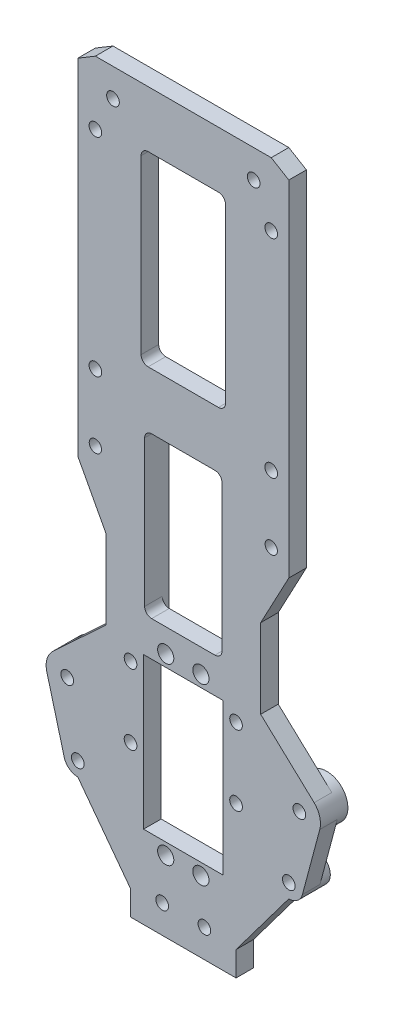
SolidWorks part; units mm, degrees
ref_plane "正面" through (0, 0, 0) normal (0, 0, 1) x (1, 0, 0)
ref_plane "平面" through (0, 0, 0) normal (0, 1, 0) x (1, 0, 0)
ref_plane "右側面" through (0, 0, 0) normal (1, 0, 0) x (0, 0, -1)
sketch "ｽｹｯﾁ1" plane through (0, 0, 0) normal (0, 0, 1) x (1, 0, 0)
  line L4 (7.743, 43.8914) -> (57.743, 43.8914)
  line L10 (17.743, -156.1086) -> (17.743, -163.1086)
  line L14 (65.743, -113.1086) -> (32.743, -113.1086) construction
  line L16 (32.743, 95.8492) -> (32.743, -203.2608) construction
  line L17 (32.743, -113.1086) -> (-0.257, -113.1086) construction
  line L21 (17.743, -163.1086) -> (47.743, -163.1086)
  line L22 (47.743, -163.1086) -> (47.743, -156.1086)
  line L25 (65.743, -89.0701) -> (65.743, -113.1086) construction
  line L26 (26.743, -155.1086) -> (38.743, -155.1086) construction
  line L27 (-0.257, -123.1086) -> (-0.257, -103.1086) construction
  line L34 (2.743, -132.1086) -> (62.743, -132.1086) construction
  line L36 (-41.4825, 1.8914) -> (140.922, 1.8914) construction
  line L38 (10.743, -94.6763) -> (10.743, -72.1086)
  line L39 (54.743, -94.6763) -> (54.743, -72.1086)
  line L41 (54.743, -72.1086) -> (62.743, -57.1086)
  line L42 (62.743, -57.1086) -> (62.743, 40.8914)
  line L43 (16.0734, -118.1086) -> (50.1368, -118.1086) construction
  line L48 (27.743, -93.3086) -> (37.743, -93.3086) construction
  line L49 (21.443, -96.6086) -> (44.043, -96.6086)
  line L50 (21.443, -96.6086) -> (21.443, -139.6086)
  line L52 (44.043, -96.6086) -> (44.043, -139.6086)
  line L53 (21.443, -96.6086) -> (44.043, -139.6086) construction
  line L54 (21.443, -139.6086) -> (44.043, -96.6086) construction
  line L55 (37.743, -93.3086) -> (37.743, -142.9086) construction
  line L56 (37.743, -142.9086) -> (27.743, -142.9086) construction
  line L57 (27.743, -142.9086) -> (27.743, -93.3086) construction
  line L58 (62.743, 40.8914) -> (57.743, 43.8914)
  line L59 (7.743, 43.8914) -> (2.743, 40.8914)
  line L60 (2.743, 40.8914) -> (2.743, -57.1086)
  line L61 (2.743, -57.1086) -> (10.743, -72.1086)
  line L62 (69.9508, -108.8314) -> (54.743, -94.6763)
  line L64 (-4.5045, -108.8708) -> (10.743, -94.6763)
  line L65 (62.743, -136.1086) -> (47.743, -156.1086)
  line L66 (21.443, -139.6086) -> (32.743, -139.6086)
  line L67 (20.743, 27.8914) -> (44.743, 27.8914)
  line L68 (20.743, 27.8914) -> (20.743, -25.1086)
  line L69 (20.743, -25.1086) -> (44.743, -25.1086)
  line L70 (44.743, 27.8914) -> (44.743, -25.1086)
  line L71 (44.043, -139.6086) -> (32.743, -139.6086)
  line L73 (21.743, -86.6086) -> (43.743, -86.6086)
  line L82 (21.743, -86.6086) -> (21.743, -41.1086)
  line L83 (21.743, -41.1086) -> (43.743, -41.1086)
  line L84 (43.743, -86.6086) -> (43.743, -41.1086)
  line L93 (17.743, -156.1086) -> (2.743, -136.1086)
  line L95 (71.5402, -114.6555) -> (66.6078, -133.1399)
  line L96 (-6.0542, -114.6555) -> (-1.1218, -133.1399)
  line L97 (62.743, -136.1086) -> (2.743, -136.1086) construction
  line L98 (-1.1218, -133.1399) -> (80.8725, -133.1399) construction
  line L99 (12.743, 35.8914) -> (57.743, 35.8914) construction
  line L100 (4.743, -33.1086) -> (60.743, -33.1086) construction
  line L101 (-6.0542, -114.6555) -> (71.5402, -114.6555) construction
  line L102 (62.743, -57.1086) -> (2.743, -57.1086) construction
  line L103 (10.743, -72.1086) -> (54.743, -72.1086) construction
  circle A14 centre (27.743, -93.3086) radius 2.3
  circle A15 centre (37.743, -93.3086) radius 2.3
  circle A16 centre (27.743, -142.9086) radius 2.3
  circle A17 centre (37.743, -142.9086) radius 2.3
  circle A18 centre (-0.257, -113.1086) radius 1.8
  circle A20 centre (62.743, -132.1086) radius 1.8
  circle A21 centre (2.743, -132.1086) radius 1.8
  circle A30 centre (65.743, -113.1086) radius 1.8
  circle A35 centre (26.743, -155.1086) radius 1.8
  circle A36 centre (38.743, -155.1086) radius 1.8
  arc A38 (-6.0542, -114.6555) -> (-4.5045, -108.8708) centre (-0.257, -113.1086) cw
  arc A39 (71.5402, -114.6555) -> (69.9508, -108.8314) centre (65.743, -113.1086) ccw
  arc A40 (-1.1218, -133.1399) -> (2.743, -136.1086) centre (2.743, -132.1086) ccw
  arc A41 (66.6078, -133.1399) -> (62.743, -136.1086) centre (62.743, -132.1086) cw
  circle A42 centre (52.743, 35.8914) radius 1.8
  circle A43 centre (12.743, 35.8914) radius 1.8
  circle A44 centre (57.743, -33.1086) radius 1.8
  circle A45 centre (7.743, -33.1086) radius 1.8
  point P30 (32.743, -118.1086)
  point P49 (32.743, -142.9086)
  point P62 (32.743, 6.8914)
  dimension "D5" = 115
  dimension "D12" = 3
  dimension "D16" = 25
  dimension "D19" = 3.6
  dimension "D27" = 3.6
  dimension "D28" = 20
  dimension "D34" = 24.8
  dimension "D9" = 30
  dimension "D37" = 4.6
  dimension "D38" = 25
  dimension "D48" = 3.6
  dimension "D6" = 6
  dimension "D7" = 6
  dimension "D21" = 3.6
  dimension "D26" = 20
  dimension "D2" = 33
  dimension "D3" = 19
  dimension "D4" = 15
  dimension "D8" = 43
  dimension "D10" = 42
  dimension "D11" = 30
  dimension "D13" = 25
  dimension "D14" = 33
  dimension "D15" = 30
  dimension "D17" = 22.6
  dimension "D18" = 43
  dimension "D20" = 30
  dimension "D22" = 34
  dimension "D23" = 35
  dimension "D24" = 50
  dimension "D25" = 15
  dimension "D29" = 8
  dimension "D30" = 6
  dimension "D31" = 6
  dimension "D32" = 5
  dimension "D33" = 24.8
  dimension "D35" = 5
  dimension "D36" = 5
  dimension "D39" = 24
  dimension "D40" = 8
  dimension "D41" = 10
  dimension "D42" = 25
  dimension "D43" = 8
  dimension "D44" = 8
  dimension "D45" = 12
  dimension "D46" = 22
  dimension "D47" = 22
  dimension "D49" = 59
  dimension "D50" = 4
  dimension "D51" = 15
extrude "ﾎﾞｽ - 押し出し1" add sketch "ｽｹｯﾁ1" along normal blind 5
sketch "ｽｹｯﾁ3" plane through (0, 0, 5) normal (0, 0, 1) x (1, 0, 0)
  line L0 (-20.5754, -52.1086) -> (71.6894, -52.1086) construction
  line L5 (-41.4825, 1.8914) -> (140.922, 1.8914) construction
  line L7 (57.743, -20.728) -> (57.743, -85.4424) construction
  line L9 (-13.1542, 25.8914) -> (75.6263, 25.8914) construction
  line L10 (32.743, 95.8492) -> (32.743, -203.2608) construction
  line L11 (7.743, -20.728) -> (7.743, -90.4395) construction
  circle A0 centre (7.743, -52.1086) radius 1.75
  circle A1 centre (57.743, -52.1086) radius 1.75
  circle A4 centre (7.743, 25.8914) radius 1.8
  circle A5 centre (57.743, 25.8914) radius 1.8
  dimension "D7" = 3.6
  dimension "D1" = 54
  dimension "D2" = 78
  dimension "D3" = 25
  dimension "D4" = 25
  dimension "D5" = 25
  dimension "D6" = 25
extrude "ｶｯﾄ - 押し出し1" cut sketch "ｽｹｯﾁ3" against normal through all
sketch "ｽｹｯﾁ4" plane through (0, 0, 0) normal (0, 0, -1) x (-1, 0, 0)
  circle A0 centre (-7.743, 25.8914) radius 3
  circle A2 centre (-57.743, 25.8914) radius 3
  circle A6 centre (-7.743, -52.1086) radius 3
  circle A7 centre (-57.743, -52.1086) radius 3
  dimension "D1" = 6
sketch "ｽｹｯﾁ5" plane through (0, 0, 5) normal (0, 0, 1) x (1, 0, 0)
  line L0 (12.2125, -100.1086) -> (53.2964, -100.1086) construction
  line L1 (11.1967, -120.1086) -> (53.2964, -120.1086) construction
  line L2 (32.743, 95.8492) -> (32.743, -203.2608) construction
  line L4 (16.0734, -118.1086) -> (50.1368, -118.1086) construction
  circle A2 centre (47.743, -100.1086) radius 1.8
  circle A3 centre (47.743, -120.1086) radius 1.8
  circle A4 centre (17.743, -120.1086) radius 1.8
  circle A5 centre (17.743, -100.1086) radius 1.8
  dimension "D2" = 3.6
  dimension "D1" = 20
  dimension "D3" = 15
  dimension "D4" = 15
  dimension "D5" = 2
extrude "ｶｯﾄ - 押し出し3" cut sketch "ｽｹｯﾁ5" against normal blind 6
sketch "ｽｹｯﾁ7" plane through (0, 0, 0) normal (0, 0, -1) x (-1, 0, 0)
  circle A0 centre (-65.743, -113.1086) radius 6
  circle A1 centre (-62.743, -132.1086) radius 4
  circle A2 centre (0.257, -113.1086) radius 6
  circle A3 centre (-2.743, -132.1086) radius 4
  circle A4 centre (0.257, -113.1086) radius 1.8
  circle A5 centre (-2.743, -132.1086) radius 1.8
  circle A6 centre (-65.743, -113.1086) radius 1.8
  circle A7 centre (-62.743, -132.1086) radius 1.8
  dimension "D1" = 8
extrude "ﾎﾞｽ - 押し出し2" add sketch "ｽｹｯﾁ7" along normal blind 2.8
fillet "ﾌｨﾚｯﾄ1" radius 2 8 edges at (20.743, -25.1086, 2.5) (44.743, -25.1086, 2.5) (20.743, 27.8914, 2.5) (44.743, 27.8914, 2.5) (43.743, -41.1086, 2.5) (21.743, -41.1086, 2.5) (21.743, -86.6086, 2.5) (43.743, -86.6086, 2.5)
sketch "ｽｹｯﾁ8" plane through (0, 0, 0) normal (0, 0, -1) x (-1, 0, 0)
  line L0 (-32.743, 95.8492) -> (-32.743, -203.2608) construction
  line L1 (-42.743, 30.8914) -> (-22.743, 30.8914)
  line L2 (-42.743, 30.8914) -> (-42.743, 27.8914)
  line L3 (-42.743, 27.8914) -> (-22.743, 27.8914)
  line L4 (-22.743, 30.8914) -> (-22.743, 27.8914)
  line L5 (-12.743, 35.8914) -> (-57.743, 35.8914) construction
  line L6 (-4.743, -33.1086) -> (-60.743, -33.1086) construction
  line L7 (-46.743, -38.1086) -> (-18.4615, -38.1086)
  line L8 (-46.743, -38.1086) -> (-46.743, -41.1113)
  line L10 (-18.4615, -38.1086) -> (-18.4615, -40.6701)
  line L13 (-43.743, -41.1113) -> (-43.743, -94.3013)
  line L14 (-43.743, -94.3013) -> (-46.743, -94.3013)
  line L15 (-46.743, -41.1113) -> (-46.743, -94.3013)
  line L18 (-21.743, -41.1086) -> (-21.743, -94.3013)
  line L19 (-21.743, -94.3013) -> (-18.4615, -94.3013)
  line L20 (-18.4615, -40.6701) -> (-18.4615, -94.3013)
  line L21 (-43.743, -41.1113) -> (-21.743, -41.1086)
  dimension "D1" = 10
  dimension "D2" = 10
  dimension "D3" = 3
  dimension "D4" = 5
  dimension "D5" = 5
  dimension "D7" = 3
extrude "ﾎﾞｽ - 押し出し3" add sketch "ｽｹｯﾁ8" along normal blind 2
chamfer "面取り1" distance 2 angle 45 2 edges at (20.1022, -94.3013, 0) (45.243, -94.3013, 0)
ref_plane "平面1" through (62.743, -57.1086, 5) normal (0, 1, 0) x (1, 0, 0)
